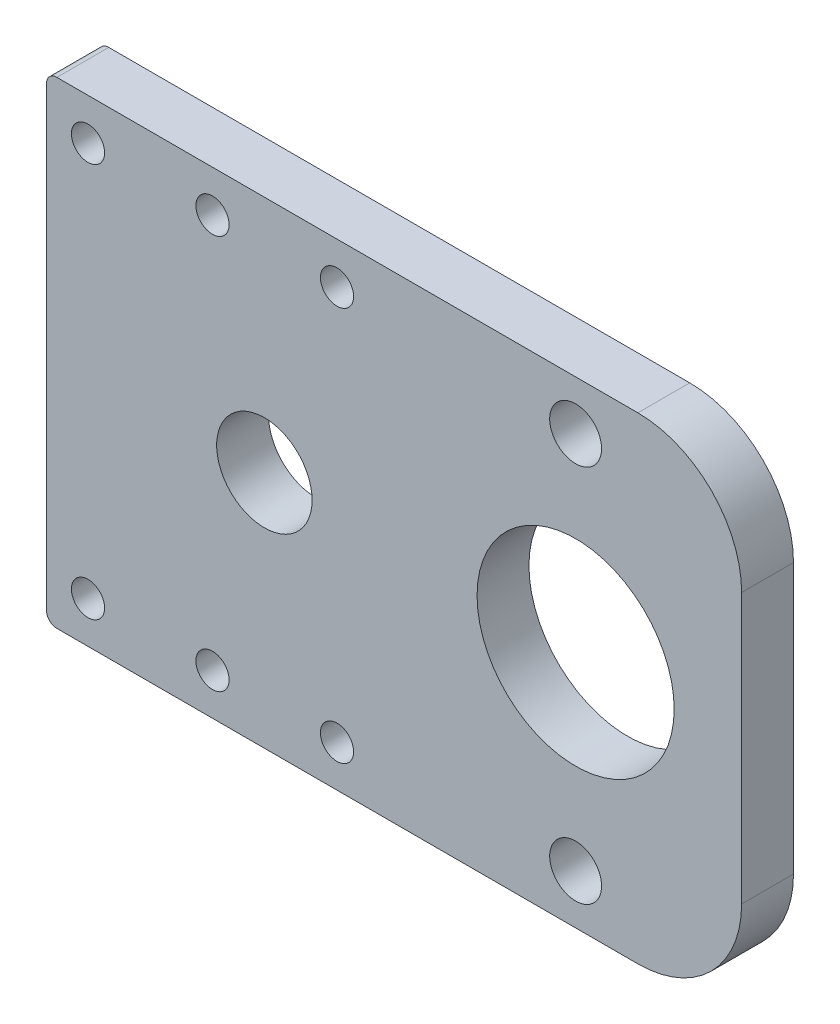
SolidWorks part; units mm, degrees
material "Acrylic (Medium-high impact)"
ref_plane "Front Plane" through (0, 0, 0) normal (0, 0, 1) x (1, 0, 0)
ref_plane "Top Plane" through (0, 0, 0) normal (0, 1, 0) x (1, 0, 0)
ref_plane "Right Plane" through (0, 0, 0) normal (1, 0, 0) x (0, 0, -1)
sketch "Sketch1" plane through (0, 0, 0) normal (0, 0, 1) x (1, 0, 0)
  line L0 (-25.3491, 0) -> (24.7222, 0) construction
  line L1 (40, -23) -> (-40, -23)
  line L2 (40, -23) -> (40, 23)
  line L3 (40, 23) -> (-40, 23)
  line L4 (-40, -23) -> (-40, 23)
  line L5 (40, -23) -> (-40, 23) construction
  line L6 (40, 23) -> (-40, -23) construction
  line L7 (30, 0) -> (30, 18.25)
  line L8 (-40, 23) -> (-25, 23)
  line L9 (-25, 23) -> (-25, -23)
  circle A0 centre (0, 0) radius 4.6
  circle A1 centre (30, 0) radius 9.5
  circle A2 centre (30, 18.25) radius 2.5
  circle A3 centre (30, -18.25) radius 2.5
  point P0 (0, 0)
  dimension "D1" = 9.2
  dimension "D2" = 19
  dimension "D7" = 5
  dimension "D3" = 46
  dimension "D4" = 30
  dimension "D5" = 80
  dimension "D6" = 18.25
  dimension "D8" = 15
extrude "Boss-Extrude1" add sketch "Sketch1" along normal blind 5 contours L4 L1 L2 L3 A0 A2 A1 A3 region at (4.899, 0, 0)
sketch "Sketch2" plane through (0, 0, 5) normal (0, 0, 1) x (1, 0, 0)
  line L0 (-25, -23) -> (-25, 23)
  line L1 (-25, -23) -> (-5, -23)
  line L2 (-25, 23) -> (-5, 23)
  line L3 (-5, -23) -> (-5, 23)
  line L4 (-25, 23) -> (-25, -23)
  line L5 (-25, -23) -> (40, -23)
  line L6 (40, -23) -> (40, 23)
  line L7 (40, 23) -> (-25, 23)
  line L9 (-25, -23) -> (40, -23)
  line L10 (40, -23) -> (40, 23)
  line L11 (40, 23) -> (-25, 23)
  line L12 (-17, 19) -> (-25, 19)
  line L13 (-17, 19) -> (-5, 19)
  line L14 (-5, 19) -> (7, 19)
  line L16 (-5, 0) -> (-25, 0)
  line L20 (-25, 23) -> (-25, -23)
  circle A0 centre (-17, 19) radius 1.6
  circle A1 centre (-5, 19) radius 1.6
  circle A5 centre (7, 19) radius 1.6
  circle A6 centre (7, -19) radius 1.6
  circle A7 centre (-5, -19) radius 1.6
  circle A8 centre (-17, -19) radius 1.6
  dimension "D5" = 3.2
  dimension "D6" = 3.2
  dimension "D7" = 19
  dimension "D8" = 3.2
  dimension "D2" = 20
  dimension "D3" = 12
  dimension "D4" = 12
  dimension "D9" = 8
  dimension "D1" = 0
extrude "Cut-Extrude1" cut sketch "Sketch2" against normal blind 10 contours A8 | A7 L3 | A7 L3 | A6 | A5 | L14 A1 L3 | L3 A1 L13 | L13 A1 L3 | L3 A1 L14 | L13 A0 L12 | L12 A0 L13 region at (7, 20.5547, 5) region at (-5.6791, -19, 5) region at (-4.3209, -19, 5) region at (-17, 19.6791, 5) region at (-17, 18.3209, 5) region at (-5.6791, 18.3209, 5) region at (-4.3209, 18.3209, 5) region at (-5.6791, 19.6791, 5) region at (-4.3209, 19.6791, 5) region at (7, -19, 5) region at (-17, -19, 5)
sketch "Sketch3" plane through (0, 0, 5) normal (0, 0, 1) x (1, 0, 0)
  line L0 (-25, 23) -> (-21, 23)
  line L1 (-21, 23) -> (-21, -23)
  line L4 (40, 23) -> (-25, 23)
  line L5 (-25, 23) -> (-25, -23)
  line L6 (-25, -23) -> (40, -23)
  line L7 (40, -23) -> (40, 23)
  line L8 (40, 23) -> (-25, 23)
  line L9 (-25, 23) -> (-25, -23)
  line L10 (-25, -23) -> (40, -23)
  line L11 (40, -23) -> (40, 23)
  line M10 (40, 23) -> (-25, 23)
  line M11 (-25, 23) -> (-25, -23)
  line M12 (-25, -23) -> (40, -23)
  dimension "D2" = 4
  dimension "D1" = 0
extrude "Cut-Extrude2" cut sketch "Sketch3" against normal through all contours L1 M10 M11 M12 region at (-23, 0, 5)
sketch "Sketch4" plane through (0, 0, 5) normal (0, 0, 1) x (1, 0, 0)
  line L1 (40, 23) -> (46, 23)
  line L2 (40, 23) -> (40, -23)
  line L3 (40, -23) -> (46, -23)
  line L4 (40, 23) -> (-21, 23)
  line L5 (-21, 23) -> (-21, -23)
  line L6 (-21, -23) -> (40, -23)
  line L7 (40, -23) -> (40, 23)
  line L8 (40, 23) -> (-21, 23)
  line L9 (-21, 23) -> (-21, -23)
  line L10 (-21, -23) -> (40, -23)
  line L11 (40, -23) -> (40, 23)
  line L12 (46, 23) -> (46, -23)
  line M19 (40, -23) -> (40, 23)
  dimension "D2" = 6
  dimension "D1" = 0
extrude "Boss-Extrude2" add sketch "Sketch4" against normal up to surface (5 mm away) contours L12 L1 L3 M19 region at (43, 0, 5) up to face at (-15.4, 19, 0)
fillet "Fillet1" radius 10 2 edges at (46, 23, 2.5) (46, -23, 2.5)
fillet "Fillet2" radius 1 2 edges at (-21, 23, 2.5) (-21, -23, 2.5)
